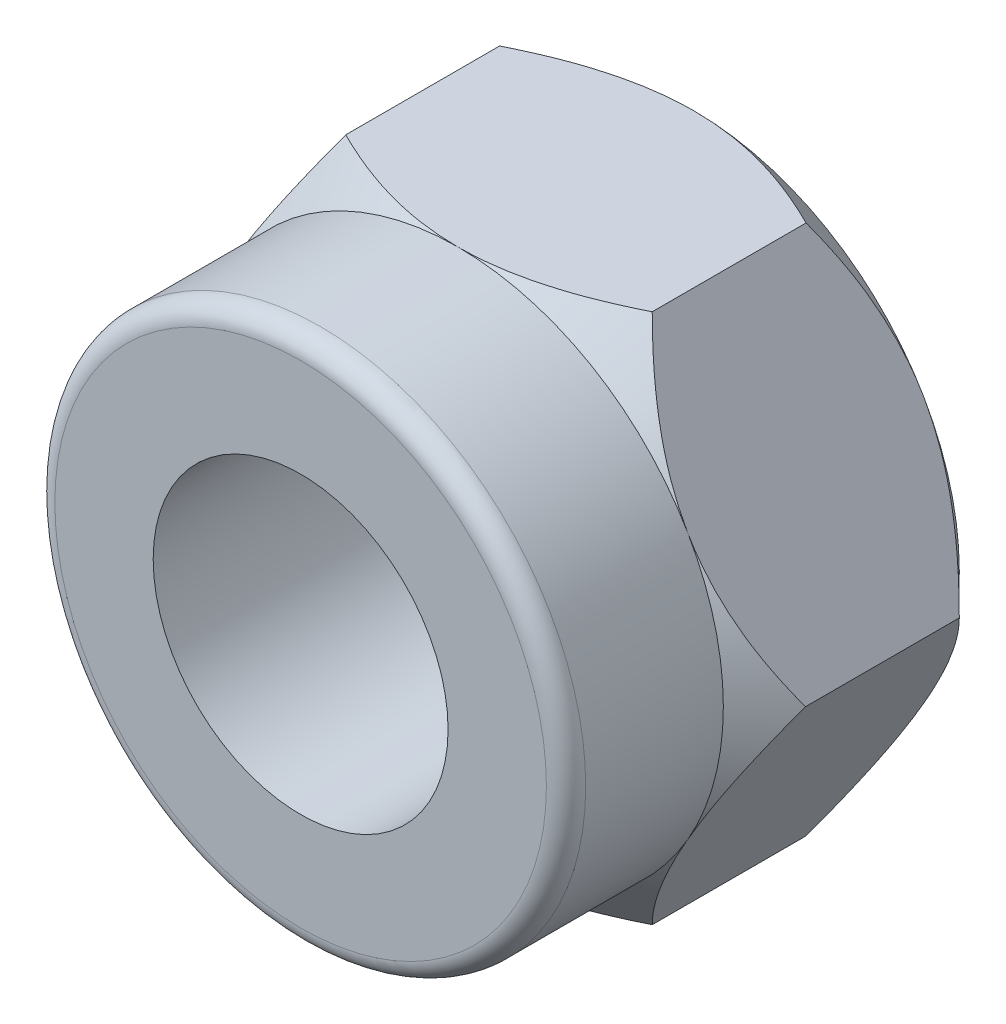
SolidWorks part; units mm, degrees
material "AISI 304"
ref_plane "前视基准面" through (0, 0, 0) normal (0, 0, 1) x (1, 0, 0)
ref_plane "上视基准面" through (0, 0, 0) normal (0, 1, 0) x (1, 0, 0)
ref_plane "右视基准面" through (0, 0, 0) normal (1, 0, 0) x (0, 0, -1)
sketch "草图1" plane through (0, 0, 0) normal (0, 0, 1) x (1, 0, 0)
  line L0 (-1.5588, 2.7) -> (1.5588, 2.7)
  line L1 (1.5588, 2.7) -> (3.1177, 0)
  line L2 (3.1177, 0) -> (1.5588, -2.7)
  line L3 (1.5588, -2.7) -> (-1.5588, -2.7)
  line L4 (-1.5588, -2.7) -> (-3.1177, 0)
  line L5 (-3.1177, 0) -> (-1.5588, 2.7)
extrude "凸台-拉伸1" add sketch "草图1" along normal blind 2.4
sketch "草图2" plane through (0, 0, 0) normal (0, 0, -1) x (-1, 0, 0)
  circle A0 centre (0, 0) radius 2.7
extrude "切除-拉伸1" cut sketch "草图2" against normal blind 4 draft 45 flip side to cut
sketch "草图3" plane through (0, 0, 2.4) normal (0, 0, 1) x (1, 0, 0)
  circle A0 centre (0, 0) radius 2.7
extrude "切除-拉伸2" cut sketch "草图3" against normal blind 4 draft 45 flip side to cut
extrude "凸台-拉伸2" add sketch "草图3<2>" along normal blind 1.6
sketch "草图3<2>" plane through (0, 0, 2.4) normal (0, 0, 1) x (1, 0, 0) same geometry as "草图3"
fillet "圆角1" radius 0.2 1 edges at (2.7, 0, 4)
sketch "草图4" plane through (0, 0, 4) normal (0, 0, 1) x (1, 0, 0)
  circle A0 centre (0, 0) radius 1.5
  dimension "D1" = 3
extrude "切除-拉伸3" cut sketch "草图4" against normal through all
